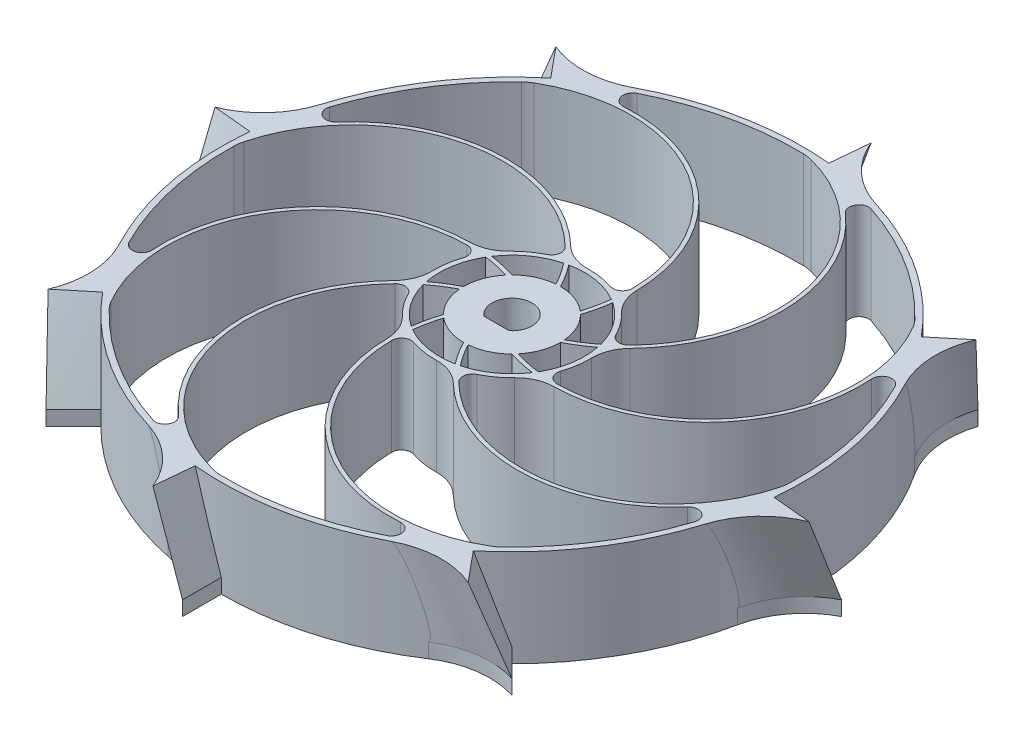
SolidWorks part; units mm, degrees
material "PET"
ref_plane "Front Plane" through (0, 0, 0) normal (0, 0, 1) x (1, 0, 0)
ref_plane "Top Plane" through (0, 0, 0) normal (0, 1, 0) x (1, 0, 0)
ref_plane "Right Plane" through (0, 0, 0) normal (1, 0, 0) x (0, 0, -1)
ref_plane "Plane1" through (0, 3, 0) normal (0, 1, 0) x (1, 0, 0)
sketch "Sketch1" plane through (0, 0, 0) normal (0, 1, 0) x (1, 0, 0)
  line L0 (-2.603, -3.2) -> (2.603, -3.2)
  arc A0 (2.603, -3.2) -> (-2.603, -3.2) centre (0, 0) ccw
  circle A1 centre (0, 0) radius 60
  circle A28 centre (0, 0) radius 10
  circle A29 centre (0, 0) radius 58.8
  point P78 (0, 0)
  dimension "D1" = 8.25
  dimension "D2" = 120
  dimension "D3" = 20
  dimension "D7" = 3.2
  dimension "D4" = 1.2
extrude "Boss-Extrude1" add sketch "Sketch1" along normal blind 20 contours A1 A29 | A28 A0 L0 region at (-59.8303, 0, 0) region at (-9.7172, 0, 0)
sketch "Sketch4" plane through (0, 0, 0) normal (0, 1, 0) x (1, 0, 0)
  line L0 (-9.6325, -0.7106) -> (-10, 0)
  line L1 (0.1172, -59.2086) -> (0, -60)
  arc A0 (0, -60) -> (-10, 0) centre (4.6819, -28.3864) cw
  circle A1 centre (0, 0) radius 60 construction
  circle A2 centre (0, 0) radius 10 construction
  arc A3 (0.1172, -59.2086) -> (-9.6325, -0.7106) centre (4.6819, -28.3864) cw
  dimension "D1" = 0.8
extrude "Boss-Extrude4" add sketch "Sketch4" along normal up to surface (20 mm away) up to face at (0, 20, 58.8)
ref_axis "Axis1" through (0, 21, 0) along (0, -1, 0)
pattern_circular "CirPattern1" count 8 over 360 about axis through (0, 21, 0) along (0, -1, 0) of "Boss-Extrude4"
sketch "Sketch2" plane through (0, 0, 0) normal (0, 1, 0) x (1, 0, 0)
  circle A0 centre (0, 0) radius 15
  circle A1 centre (0, 0) radius 16
  dimension "D1" = 30
  dimension "D2" = 1
extrude "Boss-Extrude2" add sketch "Sketch2" along normal up to surface (20 mm away) up to face at (21.0377, 20, 26.1005)
sketch "Sketch3" plane through (0, 3, 0) normal (0, 1, 0) x (1, 0, 0)
  line L0 (0, -60) -> (0, -68)
  line L6 (-42.4264, -42.4264) -> (-48.0833, -48.0833)
  line L7 (-60, 0) -> (-68, 0)
  line L8 (-42.4264, 42.4264) -> (-48.0833, 48.0833)
  line L9 (0, 60) -> (0, 68)
  line L10 (42.4264, 42.4264) -> (48.0833, 48.0833)
  line L11 (60, 0) -> (68, 0)
  line L12 (42.4264, -42.4264) -> (48.0833, -48.0833)
  arc A0 (-48.0833, -48.0833) -> (-50.1745, -32.9017) centre (-65.1067, -42.6934) ccw
  arc A1 (0, -68) -> (-12.2137, -58.7437) centre (-15.8486, -76.2261) ccw
  arc A13 (-68, 0) -> (-58.7437, 12.2137) centre (-76.2261, 15.8486) ccw
  arc A15 (-48.0833, 48.0833) -> (-32.9017, 50.1745) centre (-42.6934, 65.1067) ccw
  circle A17 centre (0, 0) radius 60 construction
  circle A18 centre (0, 0) radius 60
  arc A19 (0, 68) -> (12.2137, 58.7437) centre (15.8486, 76.2261) ccw
  arc A20 (48.0833, 48.0833) -> (50.1745, 32.9017) centre (65.1067, 42.6934) ccw
  arc A21 (68, 0) -> (58.7437, -12.2137) centre (76.2261, -15.8486) ccw
  arc A22 (48.0833, -48.0833) -> (32.9017, -50.1745) centre (42.6934, -65.1067) ccw
  arc A23 (-58.7437, 12.2137) -> (-60, 0) centre (0, 0) ccw
  arc A24 (60, 0) -> (58.7437, -12.2137) centre (0, 0) cw
  point P30 (0, 0)
  point P33 (-2.1651, 1.25)
  point P42 (0, 0)
  dimension "D1" = 8
  dimension "D2" = 8
fillet "Fillet1" radius 2 16 edges at (7.6573, 10, -14.0487) (15.3485, 10, -4.5193) (14.0487, 10, 7.6573) (4.5193, 10, 15.3485) (-7.6573, 10, 14.0487) (-15.3485, 10, 4.5193) (-14.0487, 10, -7.6573) (-4.5193, 10, -15.3485) (-6.0542, 10, 58.4875) (37.0759, 10, 45.6379) (58.4875, 10, 6.0542) (45.6379, 10, -37.0759) (6.0542, 10, -58.4875) (-37.0759, 10, -45.6379) (-58.4875, 10, -6.0542) (-45.6379, 10, 37.0759)
fillet "Fillet2" radius 8 16 edges at (-8.4195, 10, 13.6056) (-15.5741, 10, 3.6672) (-13.6056, 10, -8.4195) (-3.6672, 10, -15.5741) (8.4195, 10, -13.6056) (15.5741, 10, -3.6672) (13.6056, 10, 8.4195) (3.6672, 10, 15.5741) (-58.7555, 10, -2.2868) (-39.9294, 10, -43.1635) (2.2868, 10, -58.7555) (43.1635, 10, -39.9294) (58.7555, 10, 2.2868) (39.9294, 10, 43.1635) (-2.2868, 10, 58.7555) (-43.1635, 10, 39.9294)
sketch "Sketch5" plane through (0, 20, 0) normal (0, 1, 0) x (1, 0, 0)
  line L0 (-5.6487, -59.7335) -> (-6.4019, -67.698)
  line L6 (-46.2322, -38.2437) -> (-52.3965, -43.3429)
  line L7 (-59.7335, 5.6487) -> (-67.698, 6.4019)
  line L8 (-38.2437, 46.2322) -> (-43.3429, 52.3965)
  line L9 (5.6487, 59.7335) -> (6.4019, 67.698)
  line L10 (46.2322, 38.2437) -> (52.3965, 43.3429)
  line L11 (59.7335, -5.6487) -> (67.698, -6.4019)
  line L12 (38.2437, -46.2322) -> (43.3429, -52.3965)
  line L13 (0, 0) -> (-5.6487, -59.7335) construction
  arc A0 (-52.3965, -43.3429) -> (-53.0492, -28.0319) centre (-68.8369, -36.3743) ccw
  arc A1 (-6.4019, -67.698) -> (-17.6899, -57.333) centre (-22.9545, -74.3955) ccw
  arc A13 (-67.698, 6.4019) -> (-57.333, 17.6899) centre (-74.3955, 22.9545) ccw
  arc A15 (-43.3429, 52.3965) -> (-28.0319, 53.0492) centre (-36.3743, 68.8369) ccw
  circle A18 centre (0, 0) radius 60
  arc A19 (6.4019, 67.698) -> (17.6899, 57.333) centre (22.9545, 74.3955) ccw
  arc A20 (52.3965, 43.3429) -> (53.0492, 28.0319) centre (68.8369, 36.3743) ccw
  arc A21 (67.698, -6.4019) -> (57.333, -17.6899) centre (74.3955, -22.9545) ccw
  arc A22 (43.3429, -52.3965) -> (28.0319, -53.0492) centre (36.3743, -68.8369) ccw
  arc A23 (-57.333, 17.6899) -> (-59.7335, 5.6487) centre (0, 0) ccw
  arc A24 (59.7335, -5.6487) -> (57.333, -17.6899) centre (0, 0) cw
  circle A25 centre (0, 0) radius 60 construction
  point P3 (0, 0)
  point P4 (0, 0)
  point P5 (4.1329, -59.8575)
  point P14 (-5.6487, -59.7335)
  point P30 (0, 0)
  point P33 (-2.1651, 1.25)
  point P42 (0, 0)
  point P44 (-12.2137, -58.7437)
  point P45 (0, 0)
  dimension "D3" = 12.2782
  dimension "D1" = 8
  dimension "D2" = 8
loft "Loft1" add section "Sketch3" section "Sketch5" connector at (0, 3, 60) connector at (-5.6487, 20, 59.7335)
extrude "Boss-Extrude6" add sketch "Sketch3<82>" against normal blind 3 contours A18 A1 L0 region at (-2.8725, 3, 62.1395)
sketch "Sketch3<82>" plane through (0, 3, 0) normal (0, 1, 0) x (1, 0, 0) same geometry as "Sketch3"
pattern_circular "CirPattern2" count 8 over 360 about axis through (0, 21, 0) along (0, -1, 0) of "Boss-Extrude6", "Loft1"
